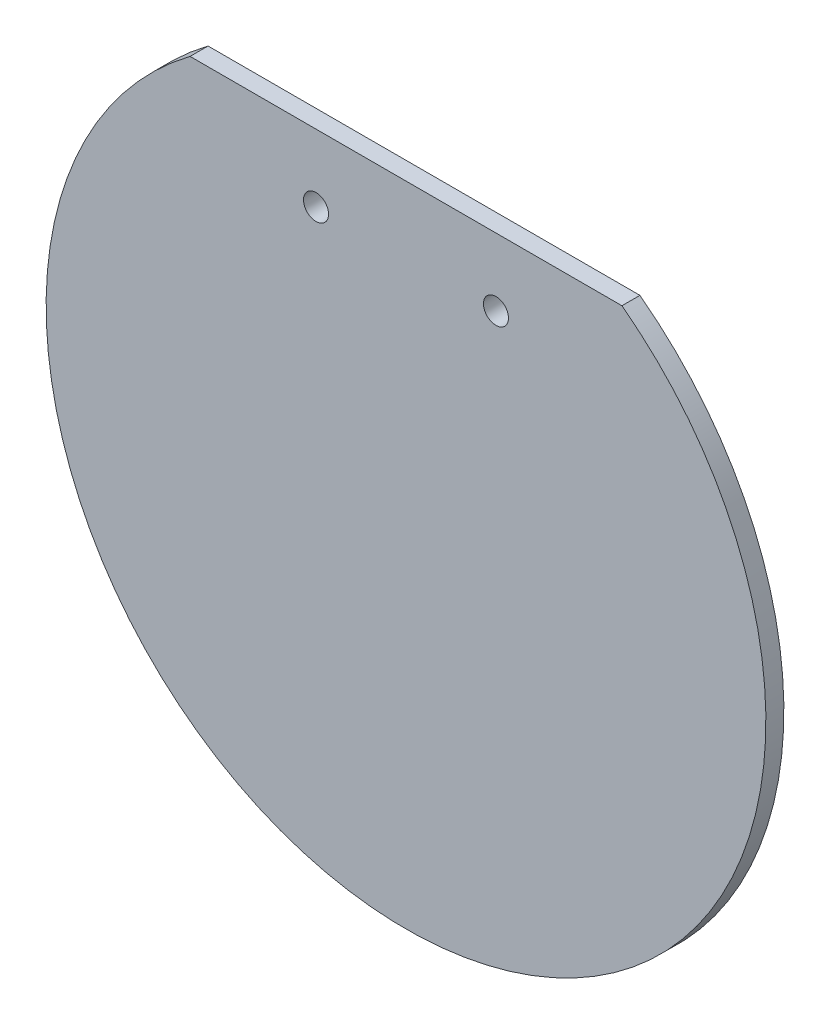
SolidWorks part; units mm, degrees
ref_plane "Front Plane" through (0, 0, 0) normal (0, 0, 1) x (1, 0, 0)
ref_plane "Top Plane" through (0, 0, 0) normal (0, 1, 0) x (1, 0, 0)
ref_plane "Right Plane" through (0, 0, 0) normal (1, 0, 0) x (0, 0, -1)
sketch "Sketch1" plane through (0, 0, 0) normal (0, 0, 1) x (1, 0, 0)
  line L0 (-19.05, 25.4) -> (19.05, 25.4) construction
  line L1 (0, 25.4) -> (0, 0) construction
  line L2 (-19.05, 25.4) -> (19.05, 25.4)
  circle A0 centre (0, 0) radius 31.75 construction
  arc A1 (-19.05, 25.4) -> (19.05, 25.4) centre (0, 0) ccw
  dimension "D1" = 38.1
  dimension "D2" = 25.4
extrude "Boss-Extrude1" add sketch "Sketch1" along normal blind 1.5875
sketch "Sketch3" plane through (0, 0, 1.5875) normal (0, 0, 1) x (1, 0, 0)
  circle A3 centre (7.9375, 19.4462) radius 1.1049
  circle A5 centre (-7.9375, 19.4462) radius 1.1049
  dimension "D1" = 2.2098
extrude "Cut-Extrude1" cut sketch "Sketch3" against normal through all
